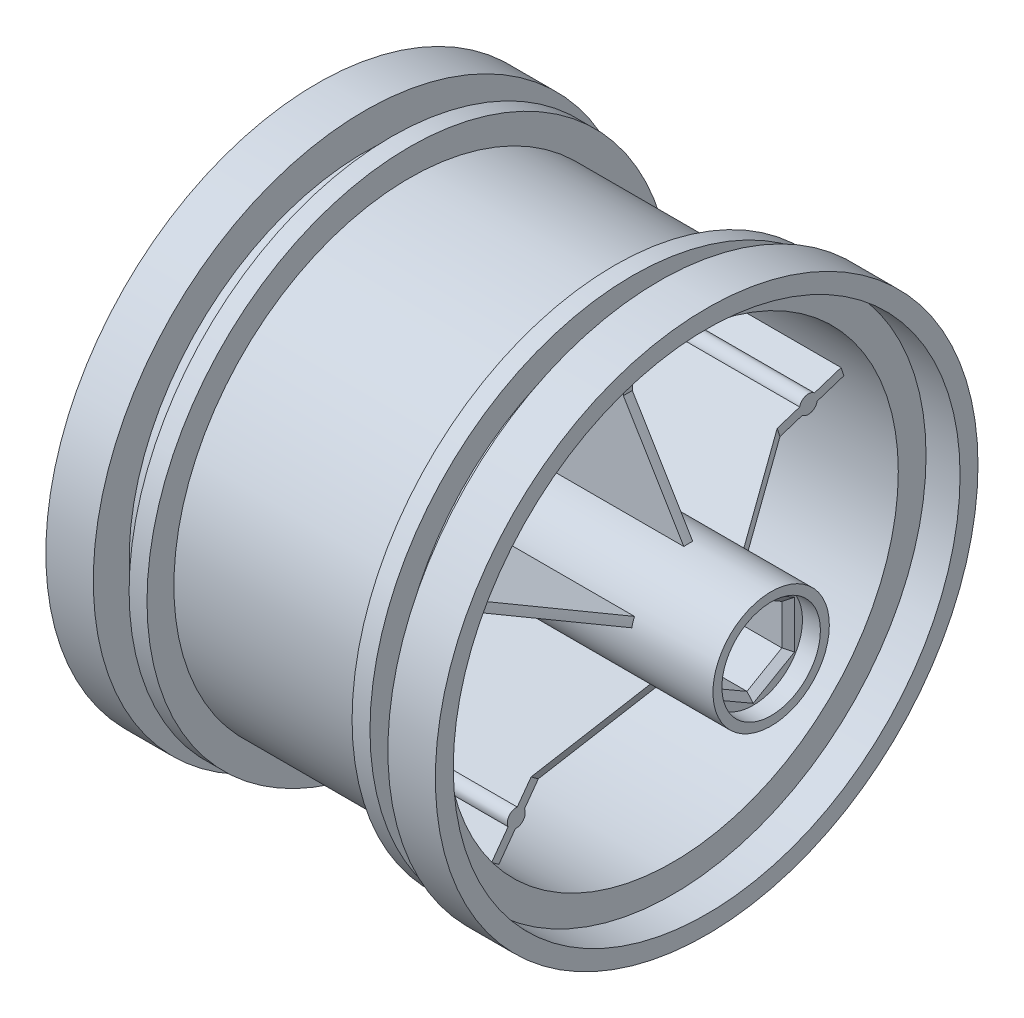
SolidWorks part; units mm, degrees
ref_plane "Front Plane" through (0, 0, 0) normal (0, 0, 1) x (1, 0, 0)
ref_plane "Top Plane" through (0, 0, 0) normal (0, 1, 0) x (1, 0, 0)
ref_plane "Right Plane" through (0, 0, 0) normal (1, 0, 0) x (0, 0, -1)
sketch "Sketch1" plane through (0, 0, 0) normal (0, 0, 1) x (1, 0, 0)
  line L0 (-16.35, 0) -> (-16.35, 8.25)
  line L2 (-32.35, 28.3) -> (-32.35, 30.3)
  line L3 (-32.35, 30.3) -> (-27.05, 30.3)
  line L4 (-27.05, 30.3) -> (-27.05, 26.3)
  line L5 (-27.05, 26.3) -> (-24.05, 26.3)
  line L6 (-24.05, 26.3) -> (-24.05, 29.3)
  line L7 (-24.05, 29.3) -> (-22.05, 29.3)
  line L8 (-22.05, 29.3) -> (-22.05, 26.3)
  line L23 (16.35, 0) -> (-16.35, 0) construction
  line L24 (-22.05, 26.3) -> (0.85, 26.3)
  line L25 (0.85, 26.3) -> (0.85, 29.3)
  line L26 (0.85, 29.3) -> (2.85, 29.3)
  line L27 (2.85, 29.3) -> (2.85, 26.3)
  line L28 (2.85, 26.3) -> (5.85, 26.3)
  line L29 (5.85, 26.3) -> (5.85, 30.3)
  line L30 (5.85, 30.3) -> (11.15, 30.3)
  line L31 (11.15, 30.3) -> (11.15, 28.3)
  line L32 (11.15, 28.3) -> (7.35, 28.3)
  line L33 (7.35, 28.3) -> (7.35, 25.2)
  line L34 (7.35, 25.2) -> (2.35, 25.2)
  line L35 (2.35, 25.2) -> (2.35, 17.7)
  line L36 (2.35, 17.7) -> (9.1, 6.5)
  line L37 (9.1, 6.5) -> (18.35, 6.5)
  line L38 (18.35, 6.5) -> (18.35, 5.5)
  line L39 (18.35, 5.5) -> (16.35, 5.5)
  line L40 (16.35, 5.5) -> (16.35, 0)
  line L41 (-27.35, 24.6) -> (-29.35, 24.6)
  line L42 (-16.35, 0) -> (16.35, 0)
  line L43 (-27.35, 24.6) -> (-14.85, 8.9408)
  line L44 (-14.85, 8.9408) -> (-14.85, 8.25)
  line L45 (-14.85, 8.25) -> (-16.35, 8.25)
  arc A1 (-32.35, 28.3) -> (-29.35, 24.6) centre (-29.35, 27.6662) ccw
  dimension "D1" = 16
  dimension "D2" = 16.5
  dimension "D3" = 5
  dimension "D4" = 5.7
  dimension "D5" = 50.7
  dimension "D6" = 13
  dimension "D7" = 3
  dimension "D8" = 43.5
  dimension "D9" = 5.3
  dimension "D10" = 3
  dimension "D11" = 2
  dimension "D12" = 2
  dimension "D13" = 5.3
  dimension "D14" = 3.8
  dimension "D15" = 2
  dimension "D16" = 5.1
  dimension "D17" = 4
  dimension "D18" = 5
  dimension "D19" = 3
  dimension "D20" = 7.5
  dimension "D21" = 60.6
  dimension "D22" = 9.25
  dimension "D23" = 2
  dimension "D24" = 1
  dimension "D25" = 2
  dimension "D26" = 2
  dimension "D27" = 17.5
  dimension "D28" = 0.6908
revolve "Revolve1" add sketch "Sketch1" angle 360 about L23
sketch "Sketch2" plane through (16.35, 0, 0) normal (1, 0, 0) x (0, 0, -1)
  line L1 (0, -4.5) -> (3.8971, -2.25)
  line L2 (3.8971, -2.25) -> (3.8971, 2.25)
  line L3 (3.8971, 2.25) -> (0, 4.5)
  line L4 (0, 4.5) -> (-3.8971, 2.25)
  line L5 (-3.8971, 2.25) -> (-3.8971, -2.25)
  line L6 (-3.8971, -2.25) -> (0, -4.5)
  circle A0 centre (0, 0) radius 3.8971 construction
  circle A2 centre (0, 0) radius 5.5 construction
  circle A3 centre (0, 0) radius 5.5
  dimension "D1" = 4.5
extrude "Cut-Extrude2" cut sketch "Sketch2" against normal blind 13 contours L2 L3 L4 L5 L6 L1
chamfer "Chamfer1" distance 0.7 angle 45 6 edges at (16.35, -3.375, -1.9486) (16.35, -3.375, 1.9486) (16.35, 0, 3.8971) (16.35, 3.375, 1.9486) (16.35, 3.375, -1.9486) (16.35, 0, -3.8971)
sketch "Sketch3" plane through (3.35, 0, 0) normal (1, 0, 0) x (0, 0, -1)
  circle A0 centre (0, 0) radius 1.15
  dimension "D1" = 2.3
extrude "Cut-Extrude3" cut sketch "Sketch3" against normal through all
sketch "Sketch4" plane through (-16.35, 0, 0) normal (-1, 0, 0) x (0, 0, 1)
  circle A0 centre (0, 0) radius 3
  dimension "D1" = 6
extrude "Cut-Extrude4" cut sketch "Sketch4" against normal blind 19.5
sketch "Sketch6" plane through (-16.35, 0, 0) normal (-1, 0, 0) x (0, 0, 1)
  line L0 (-1, 5.4414) -> (1, 5.4414)
  line L1 (1, 5.4414) -> (1, 15.193)
  line L2 (1, 15.193) -> (-1, 15.193)
  line L3 (-1, 15.193) -> (-1, 5.4414)
  line L4 (5.4841, 0.7304) -> (14.7584, 3.7438)
  line L5 (4.866, 2.6325) -> (5.4841, 0.7304)
  line L6 (14.1404, 5.646) -> (4.866, 2.6325)
  line L7 (14.7584, 3.7438) -> (14.1404, 5.646)
  line L8 (2.3893, -4.9899) -> (8.1212, -12.8792)
  line L9 (4.0074, -3.8144) -> (2.3893, -4.9899)
  line L10 (9.7392, -11.7036) -> (4.0074, -3.8144)
  line L11 (8.1212, -12.8792) -> (9.7392, -11.7036)
  line L12 (-4.0074, -3.8144) -> (-9.7392, -11.7036)
  line L13 (-2.3893, -4.9899) -> (-4.0074, -3.8144)
  line L14 (-8.1212, -12.8792) -> (-2.3893, -4.9899)
  line L15 (-9.7392, -11.7036) -> (-8.1212, -12.8792)
  line L16 (-4.866, 2.6325) -> (-14.1404, 5.646)
  line L17 (-5.4841, 0.7304) -> (-4.866, 2.6325)
  line L18 (-14.7584, 3.7438) -> (-5.4841, 0.7304)
  line L19 (-14.1404, 5.646) -> (-14.7584, 3.7438)
  point P2 (0, 5.4414)
  point P25 (0, 0)
  dimension "D1" = 2
  dimension "D2" = 5
extrude "Boss-Extrude1" add sketch "Sketch6" against normal up to body separate body
sketch "Sketch7" plane through (-32.35, 0, 0) normal (-1, 0, 0) x (0, 0, 1)
  line L0 (-1.5, 26.4575) -> (-1, 27.2316)
  line L1 (1, 27.2316) -> (1.5, 26.4575)
  line L2 (0, 0) -> (0, 41.1939) construction
  line L3 (4.0336, 26.1912) -> (4.6836, 26.8445)
  line L4 (6.6399, 26.4287) -> (6.968, 25.5675)
  line L5 (9.3909, 24.7802) -> (10.1626, 25.2841)
  line L6 (11.9897, 24.4706) -> (12.1316, 23.56)
  line L7 (14.3378, 22.2863) -> (15.1973, 22.6186)
  line L8 (16.8154, 21.4431) -> (16.7649, 20.5229)
  line L9 (18.6581, 18.8182) -> (19.5679, 18.9647)
  line L10 (20.9062, 17.4784) -> (20.6655, 16.5888)
  line L11 (22.1629, 14.5278) -> (23.0833, 14.4818)
  line L12 (24.0833, 12.7498) -> (23.6629, 11.9297)
  line L13 (24.6991, 9.6024) -> (25.5898, 9.3661)
  line L14 (26.2079, 7.464) -> (25.6261, 6.7492)
  line L15 (26.1558, 4.2573) -> (26.9779, 3.841)
  line L16 (27.187, 1.852) -> (26.4694, 1.2738)
  line L17 (26.4694, -1.2738) -> (27.187, -1.852)
  line L18 (26.9779, -3.841) -> (26.1558, -4.2573)
  line L19 (25.6261, -6.7492) -> (26.2079, -7.464)
  line L20 (25.5898, -9.3661) -> (24.6991, -9.6024)
  line L21 (23.6629, -11.9297) -> (24.0833, -12.7498)
  line L22 (23.0833, -14.4818) -> (22.1629, -14.5278)
  line L23 (20.6655, -16.5888) -> (20.9062, -17.4784)
  line L24 (19.5679, -18.9647) -> (18.6581, -18.8182)
  line L25 (16.7649, -20.5229) -> (16.8154, -21.4431)
  line L26 (15.1973, -22.6186) -> (14.3378, -22.2863)
  line L27 (12.1316, -23.56) -> (11.9897, -24.4706)
  line L28 (10.1626, -25.2841) -> (9.3909, -24.7802)
  line L29 (6.968, -25.5675) -> (6.6399, -26.4287)
  line L30 (4.6836, -26.8445) -> (4.0336, -26.1912)
  line L31 (1.5, -26.4575) -> (1, -27.2316)
  line L32 (-1, -27.2316) -> (-1.5, -26.4575)
  line L33 (-4.0336, -26.1912) -> (-4.6836, -26.8445)
  line L34 (-6.6399, -26.4287) -> (-6.968, -25.5675)
  line L35 (-9.3909, -24.7802) -> (-10.1626, -25.2841)
  line L36 (-11.9897, -24.4706) -> (-12.1316, -23.56)
  line L37 (-14.3378, -22.2863) -> (-15.1973, -22.6186)
  line L38 (-16.8154, -21.4431) -> (-16.7649, -20.5229)
  line L39 (-18.6581, -18.8182) -> (-19.5679, -18.9647)
  line L40 (-20.9062, -17.4784) -> (-20.6655, -16.5888)
  line L41 (-22.1629, -14.5278) -> (-23.0833, -14.4818)
  line L42 (-24.0833, -12.7498) -> (-23.6629, -11.9297)
  line L43 (-24.6991, -9.6024) -> (-25.5898, -9.3661)
  line L44 (-26.2079, -7.464) -> (-25.6261, -6.7492)
  line L45 (-26.1558, -4.2573) -> (-26.9779, -3.841)
  line L46 (-27.187, -1.852) -> (-26.4694, -1.2738)
  line L47 (-26.4694, 1.2738) -> (-27.187, 1.852)
  line L48 (-26.9779, 3.841) -> (-26.1558, 4.2573)
  line L49 (-25.6261, 6.7492) -> (-26.2079, 7.464)
  line L50 (-25.5898, 9.3661) -> (-24.6991, 9.6024)
  line L51 (-23.6629, 11.9297) -> (-24.0833, 12.7498)
  line L52 (-23.0833, 14.4818) -> (-22.1629, 14.5278)
  line L53 (-20.6655, 16.5888) -> (-20.9062, 17.4784)
  line L54 (-19.5679, 18.9647) -> (-18.6581, 18.8182)
  line L55 (-16.7649, 20.5229) -> (-16.8154, 21.4431)
  line L56 (-15.1973, 22.6186) -> (-14.3378, 22.2863)
  line L57 (-12.1316, 23.56) -> (-11.9897, 24.4706)
  line L58 (-10.1626, 25.2841) -> (-9.3909, 24.7802)
  line L59 (-6.968, 25.5675) -> (-6.6399, 26.4287)
  line L60 (-4.6836, 26.8445) -> (-4.0336, 26.1912)
  arc A0 (1, 27.2316) -> (-1, 27.2316) centre (0, 0) ccw
  arc A1 (1.5, 26.4575) -> (-1.5, 26.4575) centre (0, 0) ccw
  arc A2 (6.968, 25.5675) -> (4.0336, 26.1912) centre (0, 0) ccw
  arc A3 (6.6399, 26.4287) -> (4.6836, 26.8445) centre (0, 0) ccw
  arc A4 (12.1316, 23.56) -> (9.3909, 24.7802) centre (0, 0) ccw
  arc A5 (11.9897, 24.4706) -> (10.1626, 25.2841) centre (0, 0) ccw
  arc A6 (16.7649, 20.5229) -> (14.3378, 22.2863) centre (0, 0) ccw
  arc A7 (16.8154, 21.4431) -> (15.1973, 22.6186) centre (0, 0) ccw
  arc A8 (20.6655, 16.5888) -> (18.6581, 18.8182) centre (0, 0) ccw
  arc A9 (20.9062, 17.4784) -> (19.5679, 18.9647) centre (0, 0) ccw
  arc A10 (23.6629, 11.9297) -> (22.1629, 14.5278) centre (0, 0) ccw
  arc A11 (24.0833, 12.7498) -> (23.0833, 14.4818) centre (0, 0) ccw
  arc A12 (25.6261, 6.7492) -> (24.6991, 9.6024) centre (0, 0) ccw
  arc A13 (26.2079, 7.464) -> (25.5898, 9.3661) centre (0, 0) ccw
  arc A14 (26.4694, 1.2738) -> (26.1558, 4.2573) centre (0, 0) ccw
  arc A15 (27.187, 1.852) -> (26.9779, 3.841) centre (0, 0) ccw
  arc A16 (26.1558, -4.2573) -> (26.4694, -1.2738) centre (0, 0) ccw
  arc A17 (26.9779, -3.841) -> (27.187, -1.852) centre (0, 0) ccw
  arc A18 (24.6991, -9.6024) -> (25.6261, -6.7492) centre (0, 0) ccw
  arc A19 (25.5898, -9.3661) -> (26.2079, -7.464) centre (0, 0) ccw
  arc A20 (22.1629, -14.5278) -> (23.6629, -11.9297) centre (0, 0) ccw
  arc A21 (23.0833, -14.4818) -> (24.0833, -12.7498) centre (0, 0) ccw
  arc A22 (18.6581, -18.8182) -> (20.6655, -16.5888) centre (0, 0) ccw
  arc A23 (19.5679, -18.9647) -> (20.9062, -17.4784) centre (0, 0) ccw
  arc A24 (14.3378, -22.2863) -> (16.7649, -20.5229) centre (0, 0) ccw
  arc A25 (15.1973, -22.6186) -> (16.8154, -21.4431) centre (0, 0) ccw
  arc A26 (9.3909, -24.7802) -> (12.1316, -23.56) centre (0, 0) ccw
  arc A27 (10.1626, -25.2841) -> (11.9897, -24.4706) centre (0, 0) ccw
  arc A28 (4.0336, -26.1912) -> (6.968, -25.5675) centre (0, 0) ccw
  arc A29 (4.6836, -26.8445) -> (6.6399, -26.4287) centre (0, 0) ccw
  arc A30 (-1.5, -26.4575) -> (1.5, -26.4575) centre (0, 0) ccw
  arc A31 (-1, -27.2316) -> (1, -27.2316) centre (0, 0) ccw
  arc A32 (-6.968, -25.5675) -> (-4.0336, -26.1912) centre (0, 0) ccw
  arc A33 (-6.6399, -26.4287) -> (-4.6836, -26.8445) centre (0, 0) ccw
  arc A34 (-12.1316, -23.56) -> (-9.3909, -24.7802) centre (0, 0) ccw
  arc A35 (-11.9897, -24.4706) -> (-10.1626, -25.2841) centre (0, 0) ccw
  arc A36 (-16.7649, -20.5229) -> (-14.3378, -22.2863) centre (0, 0) ccw
  arc A37 (-16.8154, -21.4431) -> (-15.1973, -22.6186) centre (0, 0) ccw
  arc A38 (-20.6655, -16.5888) -> (-18.6581, -18.8182) centre (0, 0) ccw
  arc A39 (-20.9062, -17.4784) -> (-19.5679, -18.9647) centre (0, 0) ccw
  arc A40 (-23.6629, -11.9297) -> (-22.1629, -14.5278) centre (0, 0) ccw
  arc A41 (-24.0833, -12.7498) -> (-23.0833, -14.4818) centre (0, 0) ccw
  arc A42 (-25.6261, -6.7492) -> (-24.6991, -9.6024) centre (0, 0) ccw
  arc A43 (-26.2079, -7.464) -> (-25.5898, -9.3661) centre (0, 0) ccw
  arc A44 (-26.4694, -1.2738) -> (-26.1558, -4.2573) centre (0, 0) ccw
  arc A45 (-27.187, -1.852) -> (-26.9779, -3.841) centre (0, 0) ccw
  arc A46 (-26.1558, 4.2573) -> (-26.4694, 1.2738) centre (0, 0) ccw
  arc A47 (-26.9779, 3.841) -> (-27.187, 1.852) centre (0, 0) ccw
  arc A48 (-24.6991, 9.6024) -> (-25.6261, 6.7492) centre (0, 0) ccw
  arc A49 (-25.5898, 9.3661) -> (-26.2079, 7.464) centre (0, 0) ccw
  arc A50 (-22.1629, 14.5278) -> (-23.6629, 11.9297) centre (0, 0) ccw
  arc A51 (-23.0833, 14.4818) -> (-24.0833, 12.7498) centre (0, 0) ccw
  arc A52 (-18.6581, 18.8182) -> (-20.6655, 16.5888) centre (0, 0) ccw
  arc A53 (-19.5679, 18.9647) -> (-20.9062, 17.4784) centre (0, 0) ccw
  arc A54 (-14.3378, 22.2863) -> (-16.7649, 20.5229) centre (0, 0) ccw
  arc A55 (-15.1973, 22.6186) -> (-16.8154, 21.4431) centre (0, 0) ccw
  arc A56 (-9.3909, 24.7802) -> (-12.1316, 23.56) centre (0, 0) ccw
  arc A57 (-10.1626, 25.2841) -> (-11.9897, 24.4706) centre (0, 0) ccw
  arc A58 (-4.0336, 26.1912) -> (-6.968, 25.5675) centre (0, 0) ccw
  arc A59 (-4.6836, 26.8445) -> (-6.6399, 26.4287) centre (0, 0) ccw
  point P126 (0, 0)
  dimension "D1" = 54.5
  dimension "D2" = 53
  dimension "D3" = 2
  dimension "D4" = 1
  dimension "D5" = 1.5
  dimension "D6" = 1.5
  dimension "D7" = 30
extrude "Cut-Extrude7" cut sketch "Sketch7" against normal blind 0.5
sketch "Sketch10" plane through (11.15, 0, 0) normal (1, 0, 0) x (0, 0, -1)
  line L0 (0, 6.5) -> (0, 25.2) construction
  line L1 (0.5, 25.195) -> (0.5, 22.066)
  line L2 (0.5, 20.334) -> (0.5, 6.4807)
  line L3 (-0.5, 20.334) -> (-0.5, 6.4807)
  line L4 (-0.5, 25.195) -> (-0.5, 22.066)
  line L5 (24.1164, 7.3102) -> (21.1405, 6.3432)
  line L6 (19.4933, 5.808) -> (6.3181, 1.5271)
  line L7 (19.1843, 6.7591) -> (6.009, 2.4782)
  line L8 (23.8074, 8.2612) -> (20.8315, 7.2943)
  line L9 (6.1819, 2.0086) -> (23.9666, 7.7872) construction
  line L10 (14.4048, -20.6771) -> (12.5656, -18.1457)
  line L11 (11.5475, -16.7444) -> (3.4048, -5.5369)
  line L12 (12.3565, -16.1566) -> (4.2138, -4.9491)
  line L13 (15.2138, -20.0893) -> (13.3746, -17.5579)
  line L14 (3.8206, -5.2586) -> (14.8122, -20.3872) construction
  line L15 (-15.2138, -20.0893) -> (-13.3746, -17.5579)
  line L16 (-12.3565, -16.1566) -> (-4.2138, -4.9491)
  line L17 (-11.5475, -16.7444) -> (-3.4048, -5.5369)
  line L18 (-14.4048, -20.6771) -> (-12.5656, -18.1457)
  line L19 (-3.8206, -5.2586) -> (-14.8122, -20.3872) construction
  line L20 (-23.8074, 8.2612) -> (-20.8315, 7.2943)
  line L21 (-19.1843, 6.7591) -> (-6.009, 2.4782)
  line L22 (-19.4933, 5.808) -> (-6.3181, 1.5271)
  line L23 (-24.1164, 7.3102) -> (-21.1405, 6.3432)
  line L24 (-6.1819, 2.0086) -> (-23.9666, 7.7872) construction
  arc A0 (19.4933, 5.808) -> (21.1405, 6.3432) centre (20.1624, 6.5512) ccw
  circle A1 centre (0, 0) radius 6.5 construction
  circle A3 centre (0, 0) radius 25.2 construction
  arc A4 (0.5, 20.334) -> (0.5, 22.066) centre (0, 21.2) ccw
  circle A5 centre (0, 0) radius 25.2 construction
  arc A8 (-0.5, 20.334) -> (-0.5, 22.066) centre (0, 21.2) cw
  arc A10 (19.1843, 6.7591) -> (20.8315, 7.2943) centre (20.1624, 6.5512) cw
  arc A11 (11.5475, -16.7444) -> (12.5656, -18.1457) centre (12.461, -17.1512) ccw
  arc A14 (12.3565, -16.1566) -> (13.3746, -17.5579) centre (12.461, -17.1512) cw
  arc A15 (-12.3565, -16.1566) -> (-13.3746, -17.5579) centre (-12.461, -17.1512) ccw
  arc A18 (-11.5475, -16.7444) -> (-12.5656, -18.1457) centre (-12.461, -17.1512) cw
  arc A19 (-19.1843, 6.7591) -> (-20.8315, 7.2943) centre (-20.1624, 6.5512) ccw
  arc A22 (-19.4933, 5.808) -> (-21.1405, 6.3432) centre (-20.1624, 6.5512) cw
  arc A23 (-0.5, 25.195) -> (-23.8074, 8.2612) centre (0, 0) ccw
  arc A24 (-24.1164, 7.3102) -> (-15.2138, -20.0893) centre (0, 0) ccw
  arc A25 (23.8074, 8.2612) -> (0.5, 25.195) centre (0, 0) ccw
  arc A26 (15.2138, -20.0893) -> (24.1164, 7.3102) centre (0, 0) ccw
  arc A27 (-14.4048, -20.6771) -> (14.4048, -20.6771) centre (0, 0) ccw
  arc A28 (-6.3181, 1.5271) -> (-4.2138, -4.9491) centre (0, 0) ccw
  arc A30 (-0.5, 6.4807) -> (-6.009, 2.4782) centre (0, 0) ccw
  arc A31 (6.009, 2.4782) -> (0.5, 6.4807) centre (0, 0) ccw
  arc A32 (4.2138, -4.9491) -> (6.3181, 1.5271) centre (0, 0) ccw
  arc A33 (-3.4048, -5.5369) -> (3.4048, -5.5369) centre (0, 0) ccw
  point P65 (0, 0)
  dimension "D1" = 2
  dimension "D2" = 4
  dimension "D3" = 0.5
  dimension "D4" = 5
extrude "Cut-Extrude8" cut sketch "Sketch10" against normal up to surface (35.0995 mm away) contours L3 A30 L21 A19 L20 A23 L4 A8 | L7 A31 L2 A4 L1 A25 L8 A10 | L22 A28 L16 A15 L15 A24 L23 A22 | L11 A33 L17 A18 L18 A27 L10 A11 | L6 A32 L12 A14 L13 A26 L5 A0 up to face at (-15.6, 0, 0)
sketch "Sketch11" plane through (0, 0, 0) normal (0, 0, 1) x (1, 0, 0)
  line L0 (-27.829, 25.195) -> (-12.9016, 6.4807)
  line L1 (-26.5498, 25.195) -> (-11.6225, 6.4807)
  line L2 (-27.0472, 25.8186) -> (-12.1198, 7.1043) construction
  line L3 (-12.9016, 6.4807) -> (9.1, 6.4807) construction
  line L5 (-26.5498, 25.195) -> (-27.829, 25.195)
  line L6 (-11.6225, 6.4807) -> (-12.9016, 6.4807)
  line L7 (48.7236, 0) -> (-48.7236, 0) construction
  line L8 (-27.829, 25.195) -> (-27.829, 8.2612) construction
  line L9 (-27.829, 25.195) -> (2.35, 25.195) construction
  point P15 (0, 0)
  dimension "D1" = 1
revolve "Revolve2" add sketch "Sketch11" angle 360 about L7
sketch "Sketch12" plane through (-32.35, 0, 0) normal (-1, 0, 0) x (0, 0, 1)
  line L0 (0, 0) -> (8.8168, 12.1353) construction
  line L1 (9.9303, 11.6649) -> (20.4913, 9.841)
  line L2 (8.0254, 13.0489) -> (3.0272, 22.5294)
  line L3 (14.1626, -5.8396) -> (15.6915, -16.4473)
  line L4 (14.8902, -3.6002) -> (22.3622, 4.083)
  line L5 (0, 0) -> (14.2658, -4.6353) construction
  line L6 (-1.1773, -15.274) -> (-10.7934, -20.006)
  line L7 (1.1773, -15.274) -> (10.7934, -20.006)
  line L8 (0, 0) -> (0, -15) construction
  line L9 (-14.8902, -3.6002) -> (-22.3622, 4.083)
  line L10 (-14.1626, -5.8396) -> (-15.6915, -16.4473)
  line L11 (0, 0) -> (-14.2658, -4.6353) construction
  line L12 (-8.0254, 13.0489) -> (-3.0272, 22.5294)
  line L13 (-9.9303, 11.6649) -> (-20.4913, 9.841)
  line L14 (0, 0) -> (-8.8168, 12.1353) construction
  arc A0 (7.4793, 3.4816) -> (1, 8.1892) centre (0, 0) ccw construction
  arc A1 (9.9303, 11.6649) -> (8.0254, 13.0489) centre (10.3841, 14.2925) cw
  arc A2 (3.0272, 22.5294) -> (4.0281, 23.9131) centre (3.8699, 22.9737) cw
  arc A3 (21.498, 11.2205) -> (4.0281, 23.9131) centre (0, 0) ccw
  arc A4 (20.4913, 9.841) -> (21.498, 11.2205) centre (20.6534, 10.7797) ccw
  arc A5 (14.1626, -5.8396) -> (14.8902, -3.6002) centre (16.8018, -5.4592) cw
  arc A6 (22.3622, 4.083) -> (23.9875, 3.5586) centre (23.0451, 3.4188) cw
  arc A7 (17.3146, -16.9784) -> (23.9875, 3.5586) centre (0, 0) ccw
  arc A8 (15.6915, -16.4473) -> (17.3146, -16.9784) centre (16.6344, -16.3114) ccw
  arc A9 (-1.1773, -15.274) -> (1.1773, -15.274) centre (0, -17.6665) cw
  arc A10 (10.7934, -20.006) -> (10.797, -21.7138) centre (10.3728, -20.8608) cw
  arc A11 (-10.797, -21.7138) -> (10.797, -21.7138) centre (0, 0) ccw
  arc A12 (-10.7934, -20.006) -> (-10.797, -21.7138) centre (-10.3728, -20.8608) ccw
  arc A13 (-14.8902, -3.6002) -> (-14.1626, -5.8396) centre (-16.8018, -5.4592) cw
  arc A14 (-15.6915, -16.4473) -> (-17.3146, -16.9784) centre (-16.6344, -16.3114) cw
  arc A15 (-23.9875, 3.5586) -> (-17.3146, -16.9784) centre (0, 0) ccw
  arc A16 (-22.3622, 4.083) -> (-23.9875, 3.5586) centre (-23.0451, 3.4188) ccw
  arc A17 (-8.0254, 13.0489) -> (-9.9303, 11.6649) centre (-10.3841, 14.2925) cw
  arc A18 (-20.4913, 9.841) -> (-21.498, 11.2205) centre (-20.6534, 10.7797) cw
  arc A19 (-4.0281, 23.9131) -> (-21.498, 11.2205) centre (0, 0) ccw
  arc A20 (-3.0272, 22.5294) -> (-4.0281, 23.9131) centre (-3.8699, 22.9737) ccw
  point P7 (4.8492, 6.6744)
  point P10 (8.8168, 12.1353)
  point P61 (0, 0)
  dimension "D1" = 48.5
  dimension "D2" = 15
  dimension "D3" = 5
extrude "Cut-Extrude9" cut sketch "Sketch12" against normal through all
fillet "Fillet3" radius 0.3 15 edges at (-16.35, -8.25, 0) (-16.35, -2.5494, 7.8462) (-16.35, 6.6744, 4.8492) (-16.35, 6.6744, -4.8492) (-16.35, -2.5494, -7.8462) (-16.35, -7.0763, 6.3773) (-16.35, -8.2519, 4.7593) (-16.35, -8.2519, -4.7593) (-16.35, -7.0763, -6.3773) (-16.35, 1.9764, -9.3187) (-16.35, 3.8785, -8.7007) (-16.35, 9.4734, 1) (-16.35, 9.4734, -1) (-16.35, 3.8785, 8.7007) (-16.35, 1.9764, 9.3187)
